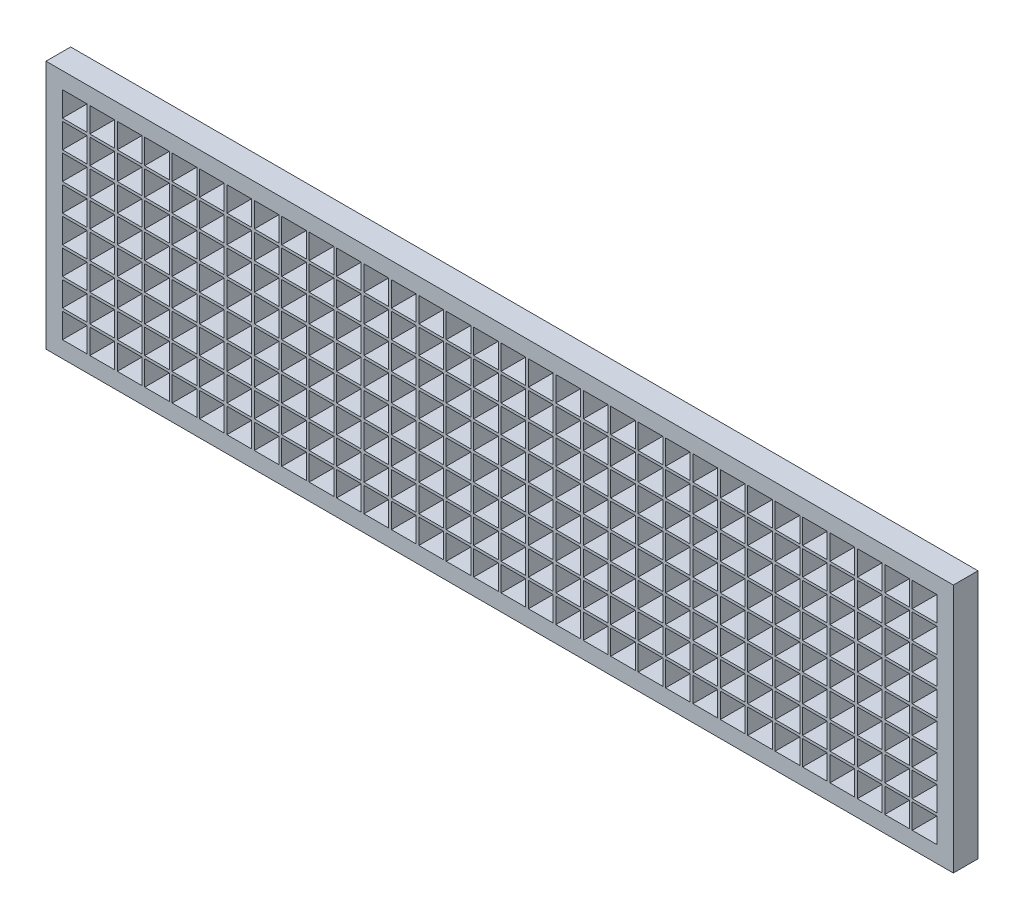
SolidWorks part; units mm, degrees
ref_plane "前视基准面" through (0, 0, 0) normal (0, 0, 1) x (1, 0, 0)
ref_plane "上视基准面" through (0, 0, 0) normal (0, 1, 0) x (1, 0, 0)
ref_plane "右视基准面" through (0, 0, 0) normal (1, 0, 0) x (0, 0, -1)
sketch "草图1" plane through (0, 0, 0) normal (0, 0, 1) x (1, 0, 0)
  line L0 (-21.8902, 5.9817) -> (-17.3902, 5.9817)
  line L1 (-26.8902, 5.9817) -> (-22.3902, 5.9817)
  line L2 (-26.8902, 5.9817) -> (-26.8902, 1.4817)
  line L3 (-26.8902, 1.4817) -> (-22.3902, 1.4817)
  line L4 (-22.3902, 5.9817) -> (-22.3902, 1.4817)
  line L5 (-21.8902, 5.9817) -> (-21.8902, 1.4817)
  line L6 (-21.8902, 1.4817) -> (-17.3902, 1.4817)
  line L7 (-17.3902, 5.9817) -> (-17.3902, 1.4817)
  line L8 (-16.8902, 5.9817) -> (-12.3902, 5.9817)
  line L9 (-16.8902, 5.9817) -> (-16.8902, 1.4817)
  line L10 (-16.8902, 1.4817) -> (-12.3902, 1.4817)
  line L11 (-12.3902, 5.9817) -> (-12.3902, 1.4817)
  line L12 (-11.8902, 5.9817) -> (-7.3902, 5.9817)
  line L13 (-11.8902, 5.9817) -> (-11.8902, 1.4817)
  line L14 (-11.8902, 1.4817) -> (-7.3902, 1.4817)
  line L15 (-7.3902, 5.9817) -> (-7.3902, 1.4817)
  line L16 (-6.8902, 5.9817) -> (-2.3902, 5.9817)
  line L17 (-6.8902, 5.9817) -> (-6.8902, 1.4817)
  line L18 (-6.8902, 1.4817) -> (-2.3902, 1.4817)
  line L19 (-2.3902, 5.9817) -> (-2.3902, 1.4817)
  line L20 (-1.8902, 5.9817) -> (2.6098, 5.9817)
  line L21 (-1.8902, 5.9817) -> (-1.8902, 1.4817)
  line L22 (-1.8902, 1.4817) -> (2.6098, 1.4817)
  line L23 (2.6098, 5.9817) -> (2.6098, 1.4817)
  line L24 (3.1098, 5.9817) -> (7.6098, 5.9817)
  line L25 (3.1098, 5.9817) -> (3.1098, 1.4817)
  line L26 (3.1098, 1.4817) -> (7.6098, 1.4817)
  line L27 (7.6098, 5.9817) -> (7.6098, 1.4817)
  line L28 (8.1098, 5.9817) -> (12.6098, 5.9817)
  line L29 (8.1098, 5.9817) -> (8.1098, 1.4817)
  line L30 (8.1098, 1.4817) -> (12.6098, 1.4817)
  line L31 (12.6098, 5.9817) -> (12.6098, 1.4817)
  line L32 (13.1098, 5.9817) -> (17.6098, 5.9817)
  line L33 (13.1098, 5.9817) -> (13.1098, 1.4817)
  line L34 (13.1098, 1.4817) -> (17.6098, 1.4817)
  line L35 (17.6098, 5.9817) -> (17.6098, 1.4817)
  line L36 (18.1098, 5.9817) -> (22.6098, 5.9817)
  line L37 (18.1098, 5.9817) -> (18.1098, 1.4817)
  line L38 (18.1098, 1.4817) -> (22.6098, 1.4817)
  line L39 (22.6098, 5.9817) -> (22.6098, 1.4817)
  line L40 (23.1098, 5.9817) -> (27.6098, 5.9817)
  line L41 (23.1098, 5.9817) -> (23.1098, 1.4817)
  line L42 (23.1098, 1.4817) -> (27.6098, 1.4817)
  line L43 (27.6098, 5.9817) -> (27.6098, 1.4817)
  line L44 (28.1098, 5.9817) -> (32.6098, 5.9817)
  line L45 (28.1098, 5.9817) -> (28.1098, 1.4817)
  line L46 (28.1098, 1.4817) -> (32.6098, 1.4817)
  line L47 (32.6098, 5.9817) -> (32.6098, 1.4817)
  line L48 (33.1098, 5.9817) -> (37.6098, 5.9817)
  line L49 (33.1098, 5.9817) -> (33.1098, 1.4817)
  line L50 (33.1098, 1.4817) -> (37.6098, 1.4817)
  line L51 (37.6098, 5.9817) -> (37.6098, 1.4817)
  line L52 (38.1098, 5.9817) -> (42.6098, 5.9817)
  line L53 (38.1098, 5.9817) -> (38.1098, 1.4817)
  line L54 (38.1098, 1.4817) -> (42.6098, 1.4817)
  line L55 (42.6098, 5.9817) -> (42.6098, 1.4817)
  line L56 (43.1098, 5.9817) -> (47.6098, 5.9817)
  line L57 (43.1098, 5.9817) -> (43.1098, 1.4817)
  line L58 (43.1098, 1.4817) -> (47.6098, 1.4817)
  line L59 (47.6098, 5.9817) -> (47.6098, 1.4817)
  line L60 (48.1098, 5.9817) -> (52.6098, 5.9817)
  line L61 (48.1098, 5.9817) -> (48.1098, 1.4817)
  line L62 (48.1098, 1.4817) -> (52.6098, 1.4817)
  line L63 (52.6098, 5.9817) -> (52.6098, 1.4817)
  line L64 (53.1098, 5.9817) -> (57.6098, 5.9817)
  line L65 (53.1098, 5.9817) -> (53.1098, 1.4817)
  line L66 (53.1098, 1.4817) -> (57.6098, 1.4817)
  line L67 (57.6098, 5.9817) -> (57.6098, 1.4817)
  line L68 (58.1098, 5.9817) -> (62.6098, 5.9817)
  line L69 (58.1098, 5.9817) -> (58.1098, 1.4817)
  line L70 (58.1098, 1.4817) -> (62.6098, 1.4817)
  line L71 (62.6098, 5.9817) -> (62.6098, 1.4817)
  line L72 (63.1098, 5.9817) -> (67.6098, 5.9817)
  line L73 (63.1098, 5.9817) -> (63.1098, 1.4817)
  line L74 (63.1098, 1.4817) -> (67.6098, 1.4817)
  line L75 (67.6098, 5.9817) -> (67.6098, 1.4817)
  line L76 (68.1098, 5.9817) -> (72.6098, 5.9817)
  line L77 (68.1098, 5.9817) -> (68.1098, 1.4817)
  line L78 (68.1098, 1.4817) -> (72.6098, 1.4817)
  line L79 (72.6098, 5.9817) -> (72.6098, 1.4817)
  line L80 (73.1098, 5.9817) -> (77.6098, 5.9817)
  line L81 (73.1098, 5.9817) -> (73.1098, 1.4817)
  line L82 (73.1098, 1.4817) -> (77.6098, 1.4817)
  line L83 (77.6098, 5.9817) -> (77.6098, 1.4817)
  line L84 (78.1098, 5.9817) -> (82.6098, 5.9817)
  line L85 (78.1098, 5.9817) -> (78.1098, 1.4817)
  line L86 (78.1098, 1.4817) -> (82.6098, 1.4817)
  line L87 (82.6098, 5.9817) -> (82.6098, 1.4817)
  line L88 (83.1098, 5.9817) -> (87.6098, 5.9817)
  line L89 (83.1098, 5.9817) -> (83.1098, 1.4817)
  line L90 (83.1098, 1.4817) -> (87.6098, 1.4817)
  line L91 (87.6098, 5.9817) -> (87.6098, 1.4817)
  line L92 (88.1098, 5.9817) -> (92.6098, 5.9817)
  line L93 (88.1098, 5.9817) -> (88.1098, 1.4817)
  line L94 (88.1098, 1.4817) -> (92.6098, 1.4817)
  line L95 (92.6098, 5.9817) -> (92.6098, 1.4817)
  line L96 (93.1098, 5.9817) -> (97.6098, 5.9817)
  line L97 (93.1098, 5.9817) -> (93.1098, 1.4817)
  line L98 (93.1098, 1.4817) -> (97.6098, 1.4817)
  line L99 (97.6098, 5.9817) -> (97.6098, 1.4817)
  line L100 (98.1098, 5.9817) -> (102.6098, 5.9817)
  line L101 (98.1098, 5.9817) -> (98.1098, 1.4817)
  line L102 (98.1098, 1.4817) -> (102.6098, 1.4817)
  line L103 (102.6098, 5.9817) -> (102.6098, 1.4817)
  line L104 (103.1098, 5.9817) -> (107.6098, 5.9817)
  line L105 (103.1098, 5.9817) -> (103.1098, 1.4817)
  line L106 (103.1098, 1.4817) -> (107.6098, 1.4817)
  line L107 (107.6098, 5.9817) -> (107.6098, 1.4817)
  line L108 (108.1098, 5.9817) -> (112.6098, 5.9817)
  line L109 (108.1098, 5.9817) -> (108.1098, 1.4817)
  line L110 (108.1098, 1.4817) -> (112.6098, 1.4817)
  line L111 (112.6098, 5.9817) -> (112.6098, 1.4817)
  line L112 (113.1098, 5.9817) -> (117.6098, 5.9817)
  line L113 (113.1098, 5.9817) -> (113.1098, 1.4817)
  line L114 (113.1098, 1.4817) -> (117.6098, 1.4817)
  line L115 (117.6098, 5.9817) -> (117.6098, 1.4817)
  line L116 (118.1098, 5.9817) -> (122.6098, 5.9817)
  line L117 (118.1098, 5.9817) -> (118.1098, 1.4817)
  line L118 (118.1098, 1.4817) -> (122.6098, 1.4817)
  line L119 (122.6098, 5.9817) -> (122.6098, 1.4817)
  line L120 (123.1098, 5.9817) -> (127.6098, 5.9817)
  line L121 (123.1098, 5.9817) -> (123.1098, 1.4817)
  line L122 (123.1098, 1.4817) -> (127.6098, 1.4817)
  line L123 (127.6098, 5.9817) -> (127.6098, 1.4817)
  line L124 (128.1098, 5.9817) -> (132.6098, 5.9817)
  line L125 (128.1098, 5.9817) -> (128.1098, 1.4817)
  line L126 (128.1098, 1.4817) -> (132.6098, 1.4817)
  line L127 (132.6098, 5.9817) -> (132.6098, 1.4817)
  line L128 (-21.8902, 10.9817) -> (-17.3902, 10.9817)
  line L129 (-21.8902, 10.9817) -> (-21.8902, 6.4817)
  line L130 (-21.8902, 6.4817) -> (-17.3902, 6.4817)
  line L131 (-17.3902, 10.9817) -> (-17.3902, 6.4817)
  line L132 (-16.8902, 10.9817) -> (-12.3902, 10.9817)
  line L133 (-16.8902, 10.9817) -> (-16.8902, 6.4817)
  line L134 (-16.8902, 6.4817) -> (-12.3902, 6.4817)
  line L135 (-12.3902, 10.9817) -> (-12.3902, 6.4817)
  line L136 (-11.8902, 10.9817) -> (-7.3902, 10.9817)
  line L137 (-11.8902, 10.9817) -> (-11.8902, 6.4817)
  line L138 (-11.8902, 6.4817) -> (-7.3902, 6.4817)
  line L139 (-7.3902, 10.9817) -> (-7.3902, 6.4817)
  line L140 (-6.8902, 10.9817) -> (-2.3902, 10.9817)
  line L141 (-6.8902, 10.9817) -> (-6.8902, 6.4817)
  line L142 (-6.8902, 6.4817) -> (-2.3902, 6.4817)
  line L143 (-2.3902, 10.9817) -> (-2.3902, 6.4817)
  line L144 (-1.8902, 10.9817) -> (2.6098, 10.9817)
  line L145 (-1.8902, 10.9817) -> (-1.8902, 6.4817)
  line L146 (-1.8902, 6.4817) -> (2.6098, 6.4817)
  line L147 (2.6098, 10.9817) -> (2.6098, 6.4817)
  line L148 (3.1098, 10.9817) -> (7.6098, 10.9817)
  line L149 (3.1098, 10.9817) -> (3.1098, 6.4817)
  line L150 (3.1098, 6.4817) -> (7.6098, 6.4817)
  line L151 (7.6098, 10.9817) -> (7.6098, 6.4817)
  line L152 (8.1098, 10.9817) -> (12.6098, 10.9817)
  line L153 (8.1098, 10.9817) -> (8.1098, 6.4817)
  line L154 (8.1098, 6.4817) -> (12.6098, 6.4817)
  line L155 (12.6098, 10.9817) -> (12.6098, 6.4817)
  line L156 (13.1098, 10.9817) -> (17.6098, 10.9817)
  line L157 (13.1098, 10.9817) -> (13.1098, 6.4817)
  line L158 (13.1098, 6.4817) -> (17.6098, 6.4817)
  line L159 (17.6098, 10.9817) -> (17.6098, 6.4817)
  line L160 (18.1098, 10.9817) -> (22.6098, 10.9817)
  line L161 (18.1098, 10.9817) -> (18.1098, 6.4817)
  line L162 (18.1098, 6.4817) -> (22.6098, 6.4817)
  line L163 (22.6098, 10.9817) -> (22.6098, 6.4817)
  line L164 (23.1098, 10.9817) -> (27.6098, 10.9817)
  line L165 (23.1098, 10.9817) -> (23.1098, 6.4817)
  line L166 (23.1098, 6.4817) -> (27.6098, 6.4817)
  line L167 (27.6098, 10.9817) -> (27.6098, 6.4817)
  line L168 (28.1098, 10.9817) -> (32.6098, 10.9817)
  line L169 (28.1098, 10.9817) -> (28.1098, 6.4817)
  line L170 (28.1098, 6.4817) -> (32.6098, 6.4817)
  line L171 (32.6098, 10.9817) -> (32.6098, 6.4817)
  line L172 (33.1098, 10.9817) -> (37.6098, 10.9817)
  line L173 (33.1098, 10.9817) -> (33.1098, 6.4817)
  line L174 (33.1098, 6.4817) -> (37.6098, 6.4817)
  line L175 (37.6098, 10.9817) -> (37.6098, 6.4817)
  line L176 (38.1098, 10.9817) -> (42.6098, 10.9817)
  line L177 (38.1098, 10.9817) -> (38.1098, 6.4817)
  line L178 (38.1098, 6.4817) -> (42.6098, 6.4817)
  line L179 (42.6098, 10.9817) -> (42.6098, 6.4817)
  line L180 (43.1098, 10.9817) -> (47.6098, 10.9817)
  line L181 (43.1098, 10.9817) -> (43.1098, 6.4817)
  line L182 (43.1098, 6.4817) -> (47.6098, 6.4817)
  line L183 (47.6098, 10.9817) -> (47.6098, 6.4817)
  line L184 (48.1098, 10.9817) -> (52.6098, 10.9817)
  line L185 (48.1098, 10.9817) -> (48.1098, 6.4817)
  line L186 (48.1098, 6.4817) -> (52.6098, 6.4817)
  line L187 (52.6098, 10.9817) -> (52.6098, 6.4817)
  line L188 (53.1098, 10.9817) -> (57.6098, 10.9817)
  line L189 (53.1098, 10.9817) -> (53.1098, 6.4817)
  line L190 (53.1098, 6.4817) -> (57.6098, 6.4817)
  line L191 (57.6098, 10.9817) -> (57.6098, 6.4817)
  line L192 (58.1098, 10.9817) -> (62.6098, 10.9817)
  line L193 (58.1098, 10.9817) -> (58.1098, 6.4817)
  line L194 (58.1098, 6.4817) -> (62.6098, 6.4817)
  line L195 (62.6098, 10.9817) -> (62.6098, 6.4817)
  line L196 (63.1098, 10.9817) -> (67.6098, 10.9817)
  line L197 (63.1098, 10.9817) -> (63.1098, 6.4817)
  line L198 (63.1098, 6.4817) -> (67.6098, 6.4817)
  line L199 (67.6098, 10.9817) -> (67.6098, 6.4817)
  line L200 (68.1098, 10.9817) -> (72.6098, 10.9817)
  line L201 (68.1098, 10.9817) -> (68.1098, 6.4817)
  line L202 (68.1098, 6.4817) -> (72.6098, 6.4817)
  line L203 (72.6098, 10.9817) -> (72.6098, 6.4817)
  line L204 (73.1098, 10.9817) -> (77.6098, 10.9817)
  line L205 (73.1098, 10.9817) -> (73.1098, 6.4817)
  line L206 (73.1098, 6.4817) -> (77.6098, 6.4817)
  line L207 (77.6098, 10.9817) -> (77.6098, 6.4817)
  line L208 (78.1098, 10.9817) -> (82.6098, 10.9817)
  line L209 (78.1098, 10.9817) -> (78.1098, 6.4817)
  line L210 (78.1098, 6.4817) -> (82.6098, 6.4817)
  line L211 (82.6098, 10.9817) -> (82.6098, 6.4817)
  line L212 (83.1098, 10.9817) -> (87.6098, 10.9817)
  line L213 (83.1098, 10.9817) -> (83.1098, 6.4817)
  line L214 (83.1098, 6.4817) -> (87.6098, 6.4817)
  line L215 (87.6098, 10.9817) -> (87.6098, 6.4817)
  line L216 (88.1098, 10.9817) -> (92.6098, 10.9817)
  line L217 (88.1098, 10.9817) -> (88.1098, 6.4817)
  line L218 (88.1098, 6.4817) -> (92.6098, 6.4817)
  line L219 (92.6098, 10.9817) -> (92.6098, 6.4817)
  line L220 (93.1098, 10.9817) -> (97.6098, 10.9817)
  line L221 (93.1098, 10.9817) -> (93.1098, 6.4817)
  line L222 (93.1098, 6.4817) -> (97.6098, 6.4817)
  line L223 (97.6098, 10.9817) -> (97.6098, 6.4817)
  line L224 (98.1098, 10.9817) -> (102.6098, 10.9817)
  line L225 (98.1098, 10.9817) -> (98.1098, 6.4817)
  line L226 (98.1098, 6.4817) -> (102.6098, 6.4817)
  line L227 (102.6098, 10.9817) -> (102.6098, 6.4817)
  line L228 (103.1098, 10.9817) -> (107.6098, 10.9817)
  line L229 (103.1098, 10.9817) -> (103.1098, 6.4817)
  line L230 (103.1098, 6.4817) -> (107.6098, 6.4817)
  line L231 (107.6098, 10.9817) -> (107.6098, 6.4817)
  line L232 (108.1098, 10.9817) -> (112.6098, 10.9817)
  line L233 (108.1098, 10.9817) -> (108.1098, 6.4817)
  line L234 (108.1098, 6.4817) -> (112.6098, 6.4817)
  line L235 (112.6098, 10.9817) -> (112.6098, 6.4817)
  line L236 (113.1098, 10.9817) -> (117.6098, 10.9817)
  line L237 (113.1098, 10.9817) -> (113.1098, 6.4817)
  line L238 (113.1098, 6.4817) -> (117.6098, 6.4817)
  line L239 (117.6098, 10.9817) -> (117.6098, 6.4817)
  line L240 (118.1098, 10.9817) -> (122.6098, 10.9817)
  line L241 (118.1098, 10.9817) -> (118.1098, 6.4817)
  line L242 (118.1098, 6.4817) -> (122.6098, 6.4817)
  line L243 (122.6098, 10.9817) -> (122.6098, 6.4817)
  line L244 (123.1098, 10.9817) -> (127.6098, 10.9817)
  line L245 (123.1098, 10.9817) -> (123.1098, 6.4817)
  line L246 (123.1098, 6.4817) -> (127.6098, 6.4817)
  line L247 (127.6098, 10.9817) -> (127.6098, 6.4817)
  line L248 (128.1098, 10.9817) -> (132.6098, 10.9817)
  line L249 (128.1098, 10.9817) -> (128.1098, 6.4817)
  line L250 (128.1098, 6.4817) -> (132.6098, 6.4817)
  line L251 (132.6098, 10.9817) -> (132.6098, 6.4817)
  line L252 (-21.8902, 15.9817) -> (-17.3902, 15.9817)
  line L253 (-21.8902, 15.9817) -> (-21.8902, 11.4817)
  line L254 (-21.8902, 11.4817) -> (-17.3902, 11.4817)
  line L255 (-17.3902, 15.9817) -> (-17.3902, 11.4817)
  line L256 (-16.8902, 15.9817) -> (-12.3902, 15.9817)
  line L257 (-16.8902, 15.9817) -> (-16.8902, 11.4817)
  line L258 (-16.8902, 11.4817) -> (-12.3902, 11.4817)
  line L259 (-12.3902, 15.9817) -> (-12.3902, 11.4817)
  line L260 (-11.8902, 15.9817) -> (-7.3902, 15.9817)
  line L261 (-11.8902, 15.9817) -> (-11.8902, 11.4817)
  line L262 (-11.8902, 11.4817) -> (-7.3902, 11.4817)
  line L263 (-7.3902, 15.9817) -> (-7.3902, 11.4817)
  line L264 (-6.8902, 15.9817) -> (-2.3902, 15.9817)
  line L265 (-6.8902, 15.9817) -> (-6.8902, 11.4817)
  line L266 (-6.8902, 11.4817) -> (-2.3902, 11.4817)
  line L267 (-2.3902, 15.9817) -> (-2.3902, 11.4817)
  line L268 (-1.8902, 15.9817) -> (2.6098, 15.9817)
  line L269 (-1.8902, 15.9817) -> (-1.8902, 11.4817)
  line L270 (-1.8902, 11.4817) -> (2.6098, 11.4817)
  line L271 (2.6098, 15.9817) -> (2.6098, 11.4817)
  line L272 (3.1098, 15.9817) -> (7.6098, 15.9817)
  line L273 (3.1098, 15.9817) -> (3.1098, 11.4817)
  line L274 (3.1098, 11.4817) -> (7.6098, 11.4817)
  line L275 (7.6098, 15.9817) -> (7.6098, 11.4817)
  line L276 (8.1098, 15.9817) -> (12.6098, 15.9817)
  line L277 (8.1098, 15.9817) -> (8.1098, 11.4817)
  line L278 (8.1098, 11.4817) -> (12.6098, 11.4817)
  line L279 (12.6098, 15.9817) -> (12.6098, 11.4817)
  line L280 (13.1098, 15.9817) -> (17.6098, 15.9817)
  line L281 (13.1098, 15.9817) -> (13.1098, 11.4817)
  line L282 (13.1098, 11.4817) -> (17.6098, 11.4817)
  line L283 (17.6098, 15.9817) -> (17.6098, 11.4817)
  line L284 (18.1098, 15.9817) -> (22.6098, 15.9817)
  line L285 (18.1098, 15.9817) -> (18.1098, 11.4817)
  line L286 (18.1098, 11.4817) -> (22.6098, 11.4817)
  line L287 (22.6098, 15.9817) -> (22.6098, 11.4817)
  line L288 (23.1098, 15.9817) -> (27.6098, 15.9817)
  line L289 (23.1098, 15.9817) -> (23.1098, 11.4817)
  line L290 (23.1098, 11.4817) -> (27.6098, 11.4817)
  line L291 (27.6098, 15.9817) -> (27.6098, 11.4817)
  line L292 (28.1098, 15.9817) -> (32.6098, 15.9817)
  line L293 (28.1098, 15.9817) -> (28.1098, 11.4817)
  line L294 (28.1098, 11.4817) -> (32.6098, 11.4817)
  line L295 (32.6098, 15.9817) -> (32.6098, 11.4817)
  line L296 (33.1098, 15.9817) -> (37.6098, 15.9817)
  line L297 (33.1098, 15.9817) -> (33.1098, 11.4817)
  line L298 (33.1098, 11.4817) -> (37.6098, 11.4817)
  line L299 (37.6098, 15.9817) -> (37.6098, 11.4817)
  line L300 (38.1098, 15.9817) -> (42.6098, 15.9817)
  line L301 (38.1098, 15.9817) -> (38.1098, 11.4817)
  line L302 (38.1098, 11.4817) -> (42.6098, 11.4817)
  line L303 (42.6098, 15.9817) -> (42.6098, 11.4817)
  line L304 (43.1098, 15.9817) -> (47.6098, 15.9817)
  line L305 (43.1098, 15.9817) -> (43.1098, 11.4817)
  line L306 (43.1098, 11.4817) -> (47.6098, 11.4817)
  line L307 (47.6098, 15.9817) -> (47.6098, 11.4817)
  line L308 (48.1098, 15.9817) -> (52.6098, 15.9817)
  line L309 (48.1098, 15.9817) -> (48.1098, 11.4817)
  line L310 (48.1098, 11.4817) -> (52.6098, 11.4817)
  line L311 (52.6098, 15.9817) -> (52.6098, 11.4817)
  line L312 (53.1098, 15.9817) -> (57.6098, 15.9817)
  line L313 (53.1098, 15.9817) -> (53.1098, 11.4817)
  line L314 (53.1098, 11.4817) -> (57.6098, 11.4817)
  line L315 (57.6098, 15.9817) -> (57.6098, 11.4817)
  line L316 (58.1098, 15.9817) -> (62.6098, 15.9817)
  line L317 (58.1098, 15.9817) -> (58.1098, 11.4817)
  line L318 (58.1098, 11.4817) -> (62.6098, 11.4817)
  line L319 (62.6098, 15.9817) -> (62.6098, 11.4817)
  line L320 (63.1098, 15.9817) -> (67.6098, 15.9817)
  line L321 (63.1098, 15.9817) -> (63.1098, 11.4817)
  line L322 (63.1098, 11.4817) -> (67.6098, 11.4817)
  line L323 (67.6098, 15.9817) -> (67.6098, 11.4817)
  line L324 (68.1098, 15.9817) -> (72.6098, 15.9817)
  line L325 (68.1098, 15.9817) -> (68.1098, 11.4817)
  line L326 (68.1098, 11.4817) -> (72.6098, 11.4817)
  line L327 (72.6098, 15.9817) -> (72.6098, 11.4817)
  line L328 (73.1098, 15.9817) -> (77.6098, 15.9817)
  line L329 (73.1098, 15.9817) -> (73.1098, 11.4817)
  line L330 (73.1098, 11.4817) -> (77.6098, 11.4817)
  line L331 (77.6098, 15.9817) -> (77.6098, 11.4817)
  line L332 (78.1098, 15.9817) -> (82.6098, 15.9817)
  line L333 (78.1098, 15.9817) -> (78.1098, 11.4817)
  line L334 (78.1098, 11.4817) -> (82.6098, 11.4817)
  line L335 (82.6098, 15.9817) -> (82.6098, 11.4817)
  line L336 (83.1098, 15.9817) -> (87.6098, 15.9817)
  line L337 (83.1098, 15.9817) -> (83.1098, 11.4817)
  line L338 (83.1098, 11.4817) -> (87.6098, 11.4817)
  line L339 (87.6098, 15.9817) -> (87.6098, 11.4817)
  line L340 (88.1098, 15.9817) -> (92.6098, 15.9817)
  line L341 (88.1098, 15.9817) -> (88.1098, 11.4817)
  line L342 (88.1098, 11.4817) -> (92.6098, 11.4817)
  line L343 (92.6098, 15.9817) -> (92.6098, 11.4817)
  line L344 (93.1098, 15.9817) -> (97.6098, 15.9817)
  line L345 (93.1098, 15.9817) -> (93.1098, 11.4817)
  line L346 (93.1098, 11.4817) -> (97.6098, 11.4817)
  line L347 (97.6098, 15.9817) -> (97.6098, 11.4817)
  line L348 (98.1098, 15.9817) -> (102.6098, 15.9817)
  line L349 (98.1098, 15.9817) -> (98.1098, 11.4817)
  line L350 (98.1098, 11.4817) -> (102.6098, 11.4817)
  line L351 (102.6098, 15.9817) -> (102.6098, 11.4817)
  line L352 (103.1098, 15.9817) -> (107.6098, 15.9817)
  line L353 (103.1098, 15.9817) -> (103.1098, 11.4817)
  line L354 (103.1098, 11.4817) -> (107.6098, 11.4817)
  line L355 (107.6098, 15.9817) -> (107.6098, 11.4817)
  line L356 (108.1098, 15.9817) -> (112.6098, 15.9817)
  line L357 (108.1098, 15.9817) -> (108.1098, 11.4817)
  line L358 (108.1098, 11.4817) -> (112.6098, 11.4817)
  line L359 (112.6098, 15.9817) -> (112.6098, 11.4817)
  line L360 (113.1098, 15.9817) -> (117.6098, 15.9817)
  line L361 (113.1098, 15.9817) -> (113.1098, 11.4817)
  line L362 (113.1098, 11.4817) -> (117.6098, 11.4817)
  line L363 (117.6098, 15.9817) -> (117.6098, 11.4817)
  line L364 (118.1098, 15.9817) -> (122.6098, 15.9817)
  line L365 (118.1098, 15.9817) -> (118.1098, 11.4817)
  line L366 (118.1098, 11.4817) -> (122.6098, 11.4817)
  line L367 (122.6098, 15.9817) -> (122.6098, 11.4817)
  line L368 (123.1098, 15.9817) -> (127.6098, 15.9817)
  line L369 (123.1098, 15.9817) -> (123.1098, 11.4817)
  line L370 (123.1098, 11.4817) -> (127.6098, 11.4817)
  line L371 (127.6098, 15.9817) -> (127.6098, 11.4817)
  line L372 (128.1098, 15.9817) -> (132.6098, 15.9817)
  line L373 (128.1098, 15.9817) -> (128.1098, 11.4817)
  line L374 (128.1098, 11.4817) -> (132.6098, 11.4817)
  line L375 (132.6098, 15.9817) -> (132.6098, 11.4817)
  line L376 (-21.8902, 20.9817) -> (-17.3902, 20.9817)
  line L377 (-21.8902, 20.9817) -> (-21.8902, 16.4817)
  line L378 (-21.8902, 16.4817) -> (-17.3902, 16.4817)
  line L379 (-17.3902, 20.9817) -> (-17.3902, 16.4817)
  line L380 (-16.8902, 20.9817) -> (-12.3902, 20.9817)
  line L381 (-16.8902, 20.9817) -> (-16.8902, 16.4817)
  line L382 (-16.8902, 16.4817) -> (-12.3902, 16.4817)
  line L383 (-12.3902, 20.9817) -> (-12.3902, 16.4817)
  line L384 (-11.8902, 20.9817) -> (-7.3902, 20.9817)
  line L385 (-11.8902, 20.9817) -> (-11.8902, 16.4817)
  line L386 (-11.8902, 16.4817) -> (-7.3902, 16.4817)
  line L387 (-7.3902, 20.9817) -> (-7.3902, 16.4817)
  line L388 (-6.8902, 20.9817) -> (-2.3902, 20.9817)
  line L389 (-6.8902, 20.9817) -> (-6.8902, 16.4817)
  line L390 (-6.8902, 16.4817) -> (-2.3902, 16.4817)
  line L391 (-2.3902, 20.9817) -> (-2.3902, 16.4817)
  line L392 (-1.8902, 20.9817) -> (2.6098, 20.9817)
  line L393 (-1.8902, 20.9817) -> (-1.8902, 16.4817)
  line L394 (-1.8902, 16.4817) -> (2.6098, 16.4817)
  line L395 (2.6098, 20.9817) -> (2.6098, 16.4817)
  line L396 (3.1098, 20.9817) -> (7.6098, 20.9817)
  line L397 (3.1098, 20.9817) -> (3.1098, 16.4817)
  line L398 (3.1098, 16.4817) -> (7.6098, 16.4817)
  line L399 (7.6098, 20.9817) -> (7.6098, 16.4817)
  line L400 (8.1098, 20.9817) -> (12.6098, 20.9817)
  line L401 (8.1098, 20.9817) -> (8.1098, 16.4817)
  line L402 (8.1098, 16.4817) -> (12.6098, 16.4817)
  line L403 (12.6098, 20.9817) -> (12.6098, 16.4817)
  line L404 (13.1098, 20.9817) -> (17.6098, 20.9817)
  line L405 (13.1098, 20.9817) -> (13.1098, 16.4817)
  line L406 (13.1098, 16.4817) -> (17.6098, 16.4817)
  line L407 (17.6098, 20.9817) -> (17.6098, 16.4817)
  line L408 (18.1098, 20.9817) -> (22.6098, 20.9817)
  line L409 (18.1098, 20.9817) -> (18.1098, 16.4817)
  line L410 (18.1098, 16.4817) -> (22.6098, 16.4817)
  line L411 (22.6098, 20.9817) -> (22.6098, 16.4817)
  line L412 (23.1098, 20.9817) -> (27.6098, 20.9817)
  line L413 (23.1098, 20.9817) -> (23.1098, 16.4817)
  line L414 (23.1098, 16.4817) -> (27.6098, 16.4817)
  line L415 (27.6098, 20.9817) -> (27.6098, 16.4817)
  line L416 (28.1098, 20.9817) -> (32.6098, 20.9817)
  line L417 (28.1098, 20.9817) -> (28.1098, 16.4817)
  line L418 (28.1098, 16.4817) -> (32.6098, 16.4817)
  line L419 (32.6098, 20.9817) -> (32.6098, 16.4817)
  line L420 (33.1098, 20.9817) -> (37.6098, 20.9817)
  line L421 (33.1098, 20.9817) -> (33.1098, 16.4817)
  line L422 (33.1098, 16.4817) -> (37.6098, 16.4817)
  line L423 (37.6098, 20.9817) -> (37.6098, 16.4817)
  line L424 (38.1098, 20.9817) -> (42.6098, 20.9817)
  line L425 (38.1098, 20.9817) -> (38.1098, 16.4817)
  line L426 (38.1098, 16.4817) -> (42.6098, 16.4817)
  line L427 (42.6098, 20.9817) -> (42.6098, 16.4817)
  line L428 (43.1098, 20.9817) -> (47.6098, 20.9817)
  line L429 (43.1098, 20.9817) -> (43.1098, 16.4817)
  line L430 (43.1098, 16.4817) -> (47.6098, 16.4817)
  line L431 (47.6098, 20.9817) -> (47.6098, 16.4817)
  line L432 (48.1098, 20.9817) -> (52.6098, 20.9817)
  line L433 (48.1098, 20.9817) -> (48.1098, 16.4817)
  line L434 (48.1098, 16.4817) -> (52.6098, 16.4817)
  line L435 (52.6098, 20.9817) -> (52.6098, 16.4817)
  line L436 (53.1098, 20.9817) -> (57.6098, 20.9817)
  line L437 (53.1098, 20.9817) -> (53.1098, 16.4817)
  line L438 (53.1098, 16.4817) -> (57.6098, 16.4817)
  line L439 (57.6098, 20.9817) -> (57.6098, 16.4817)
  line L440 (58.1098, 20.9817) -> (62.6098, 20.9817)
  line L441 (58.1098, 20.9817) -> (58.1098, 16.4817)
  line L442 (58.1098, 16.4817) -> (62.6098, 16.4817)
  line L443 (62.6098, 20.9817) -> (62.6098, 16.4817)
  line L444 (63.1098, 20.9817) -> (67.6098, 20.9817)
  line L445 (63.1098, 20.9817) -> (63.1098, 16.4817)
  line L446 (63.1098, 16.4817) -> (67.6098, 16.4817)
  line L447 (67.6098, 20.9817) -> (67.6098, 16.4817)
  line L448 (68.1098, 20.9817) -> (72.6098, 20.9817)
  line L449 (68.1098, 20.9817) -> (68.1098, 16.4817)
  line L450 (68.1098, 16.4817) -> (72.6098, 16.4817)
  line L451 (72.6098, 20.9817) -> (72.6098, 16.4817)
  line L452 (73.1098, 20.9817) -> (77.6098, 20.9817)
  line L453 (73.1098, 20.9817) -> (73.1098, 16.4817)
  line L454 (73.1098, 16.4817) -> (77.6098, 16.4817)
  line L455 (77.6098, 20.9817) -> (77.6098, 16.4817)
  line L456 (78.1098, 20.9817) -> (82.6098, 20.9817)
  line L457 (78.1098, 20.9817) -> (78.1098, 16.4817)
  line L458 (78.1098, 16.4817) -> (82.6098, 16.4817)
  line L459 (82.6098, 20.9817) -> (82.6098, 16.4817)
  line L460 (83.1098, 20.9817) -> (87.6098, 20.9817)
  line L461 (83.1098, 20.9817) -> (83.1098, 16.4817)
  line L462 (83.1098, 16.4817) -> (87.6098, 16.4817)
  line L463 (87.6098, 20.9817) -> (87.6098, 16.4817)
  line L464 (88.1098, 20.9817) -> (92.6098, 20.9817)
  line L465 (88.1098, 20.9817) -> (88.1098, 16.4817)
  line L466 (88.1098, 16.4817) -> (92.6098, 16.4817)
  line L467 (92.6098, 20.9817) -> (92.6098, 16.4817)
  line L468 (93.1098, 20.9817) -> (97.6098, 20.9817)
  line L469 (93.1098, 20.9817) -> (93.1098, 16.4817)
  line L470 (93.1098, 16.4817) -> (97.6098, 16.4817)
  line L471 (97.6098, 20.9817) -> (97.6098, 16.4817)
  line L472 (98.1098, 20.9817) -> (102.6098, 20.9817)
  line L473 (98.1098, 20.9817) -> (98.1098, 16.4817)
  line L474 (98.1098, 16.4817) -> (102.6098, 16.4817)
  line L475 (102.6098, 20.9817) -> (102.6098, 16.4817)
  line L476 (103.1098, 20.9817) -> (107.6098, 20.9817)
  line L477 (103.1098, 20.9817) -> (103.1098, 16.4817)
  line L478 (103.1098, 16.4817) -> (107.6098, 16.4817)
  line L479 (107.6098, 20.9817) -> (107.6098, 16.4817)
  line L480 (108.1098, 20.9817) -> (112.6098, 20.9817)
  line L481 (108.1098, 20.9817) -> (108.1098, 16.4817)
  line L482 (108.1098, 16.4817) -> (112.6098, 16.4817)
  line L483 (112.6098, 20.9817) -> (112.6098, 16.4817)
  line L484 (113.1098, 20.9817) -> (117.6098, 20.9817)
  line L485 (113.1098, 20.9817) -> (113.1098, 16.4817)
  line L486 (113.1098, 16.4817) -> (117.6098, 16.4817)
  line L487 (117.6098, 20.9817) -> (117.6098, 16.4817)
  line L488 (118.1098, 20.9817) -> (122.6098, 20.9817)
  line L489 (118.1098, 20.9817) -> (118.1098, 16.4817)
  line L490 (118.1098, 16.4817) -> (122.6098, 16.4817)
  line L491 (122.6098, 20.9817) -> (122.6098, 16.4817)
  line L492 (123.1098, 20.9817) -> (127.6098, 20.9817)
  line L493 (123.1098, 20.9817) -> (123.1098, 16.4817)
  line L494 (123.1098, 16.4817) -> (127.6098, 16.4817)
  line L495 (127.6098, 20.9817) -> (127.6098, 16.4817)
  line L496 (128.1098, 20.9817) -> (132.6098, 20.9817)
  line L497 (128.1098, 20.9817) -> (128.1098, 16.4817)
  line L498 (128.1098, 16.4817) -> (132.6098, 16.4817)
  line L499 (132.6098, 20.9817) -> (132.6098, 16.4817)
  line L500 (-21.8902, 25.9817) -> (-17.3902, 25.9817)
  line L501 (-21.8902, 25.9817) -> (-21.8902, 21.4817)
  line L502 (-21.8902, 21.4817) -> (-17.3902, 21.4817)
  line L503 (-17.3902, 25.9817) -> (-17.3902, 21.4817)
  line L504 (-16.8902, 25.9817) -> (-12.3902, 25.9817)
  line L505 (-16.8902, 25.9817) -> (-16.8902, 21.4817)
  line L506 (-16.8902, 21.4817) -> (-12.3902, 21.4817)
  line L507 (-12.3902, 25.9817) -> (-12.3902, 21.4817)
  line L508 (-11.8902, 25.9817) -> (-7.3902, 25.9817)
  line L509 (-11.8902, 25.9817) -> (-11.8902, 21.4817)
  line L510 (-11.8902, 21.4817) -> (-7.3902, 21.4817)
  line L511 (-7.3902, 25.9817) -> (-7.3902, 21.4817)
  line L512 (-6.8902, 25.9817) -> (-2.3902, 25.9817)
  line L513 (-6.8902, 25.9817) -> (-6.8902, 21.4817)
  line L514 (-6.8902, 21.4817) -> (-2.3902, 21.4817)
  line L515 (-2.3902, 25.9817) -> (-2.3902, 21.4817)
  line L516 (-1.8902, 25.9817) -> (2.6098, 25.9817)
  line L517 (-1.8902, 25.9817) -> (-1.8902, 21.4817)
  line L518 (-1.8902, 21.4817) -> (2.6098, 21.4817)
  line L519 (2.6098, 25.9817) -> (2.6098, 21.4817)
  line L520 (3.1098, 25.9817) -> (7.6098, 25.9817)
  line L521 (3.1098, 25.9817) -> (3.1098, 21.4817)
  line L522 (3.1098, 21.4817) -> (7.6098, 21.4817)
  line L523 (7.6098, 25.9817) -> (7.6098, 21.4817)
  line L524 (8.1098, 25.9817) -> (12.6098, 25.9817)
  line L525 (8.1098, 25.9817) -> (8.1098, 21.4817)
  line L526 (8.1098, 21.4817) -> (12.6098, 21.4817)
  line L527 (12.6098, 25.9817) -> (12.6098, 21.4817)
  line L528 (13.1098, 25.9817) -> (17.6098, 25.9817)
  line L529 (13.1098, 25.9817) -> (13.1098, 21.4817)
  line L530 (13.1098, 21.4817) -> (17.6098, 21.4817)
  line L531 (17.6098, 25.9817) -> (17.6098, 21.4817)
  line L532 (18.1098, 25.9817) -> (22.6098, 25.9817)
  line L533 (18.1098, 25.9817) -> (18.1098, 21.4817)
  line L534 (18.1098, 21.4817) -> (22.6098, 21.4817)
  line L535 (22.6098, 25.9817) -> (22.6098, 21.4817)
  line L536 (23.1098, 25.9817) -> (27.6098, 25.9817)
  line L537 (23.1098, 25.9817) -> (23.1098, 21.4817)
  line L538 (23.1098, 21.4817) -> (27.6098, 21.4817)
  line L539 (27.6098, 25.9817) -> (27.6098, 21.4817)
  line L540 (28.1098, 25.9817) -> (32.6098, 25.9817)
  line L541 (28.1098, 25.9817) -> (28.1098, 21.4817)
  line L542 (28.1098, 21.4817) -> (32.6098, 21.4817)
  line L543 (32.6098, 25.9817) -> (32.6098, 21.4817)
  line L544 (33.1098, 25.9817) -> (37.6098, 25.9817)
  line L545 (33.1098, 25.9817) -> (33.1098, 21.4817)
  line L546 (33.1098, 21.4817) -> (37.6098, 21.4817)
  line L547 (37.6098, 25.9817) -> (37.6098, 21.4817)
  line L548 (38.1098, 25.9817) -> (42.6098, 25.9817)
  line L549 (38.1098, 25.9817) -> (38.1098, 21.4817)
  line L550 (38.1098, 21.4817) -> (42.6098, 21.4817)
  line L551 (42.6098, 25.9817) -> (42.6098, 21.4817)
  line L552 (43.1098, 25.9817) -> (47.6098, 25.9817)
  line L553 (43.1098, 25.9817) -> (43.1098, 21.4817)
  line L554 (43.1098, 21.4817) -> (47.6098, 21.4817)
  line L555 (47.6098, 25.9817) -> (47.6098, 21.4817)
  line L556 (48.1098, 25.9817) -> (52.6098, 25.9817)
  line L557 (48.1098, 25.9817) -> (48.1098, 21.4817)
  line L558 (48.1098, 21.4817) -> (52.6098, 21.4817)
  line L559 (52.6098, 25.9817) -> (52.6098, 21.4817)
  line L560 (53.1098, 25.9817) -> (57.6098, 25.9817)
  line L561 (53.1098, 25.9817) -> (53.1098, 21.4817)
  line L562 (53.1098, 21.4817) -> (57.6098, 21.4817)
  line L563 (57.6098, 25.9817) -> (57.6098, 21.4817)
  line L564 (58.1098, 25.9817) -> (62.6098, 25.9817)
  line L565 (58.1098, 25.9817) -> (58.1098, 21.4817)
  line L566 (58.1098, 21.4817) -> (62.6098, 21.4817)
  line L567 (62.6098, 25.9817) -> (62.6098, 21.4817)
  line L568 (63.1098, 25.9817) -> (67.6098, 25.9817)
  line L569 (63.1098, 25.9817) -> (63.1098, 21.4817)
  line L570 (63.1098, 21.4817) -> (67.6098, 21.4817)
  line L571 (67.6098, 25.9817) -> (67.6098, 21.4817)
  line L572 (68.1098, 25.9817) -> (72.6098, 25.9817)
  line L573 (68.1098, 25.9817) -> (68.1098, 21.4817)
  line L574 (68.1098, 21.4817) -> (72.6098, 21.4817)
  line L575 (72.6098, 25.9817) -> (72.6098, 21.4817)
  line L576 (73.1098, 25.9817) -> (77.6098, 25.9817)
  line L577 (73.1098, 25.9817) -> (73.1098, 21.4817)
  line L578 (73.1098, 21.4817) -> (77.6098, 21.4817)
  line L579 (77.6098, 25.9817) -> (77.6098, 21.4817)
  line L580 (78.1098, 25.9817) -> (82.6098, 25.9817)
  line L581 (78.1098, 25.9817) -> (78.1098, 21.4817)
  line L582 (78.1098, 21.4817) -> (82.6098, 21.4817)
  line L583 (82.6098, 25.9817) -> (82.6098, 21.4817)
  line L584 (83.1098, 25.9817) -> (87.6098, 25.9817)
  line L585 (83.1098, 25.9817) -> (83.1098, 21.4817)
  line L586 (83.1098, 21.4817) -> (87.6098, 21.4817)
  line L587 (87.6098, 25.9817) -> (87.6098, 21.4817)
  line L588 (88.1098, 25.9817) -> (92.6098, 25.9817)
  line L589 (88.1098, 25.9817) -> (88.1098, 21.4817)
  line L590 (88.1098, 21.4817) -> (92.6098, 21.4817)
  line L591 (92.6098, 25.9817) -> (92.6098, 21.4817)
  line L592 (93.1098, 25.9817) -> (97.6098, 25.9817)
  line L593 (93.1098, 25.9817) -> (93.1098, 21.4817)
  line L594 (93.1098, 21.4817) -> (97.6098, 21.4817)
  line L595 (97.6098, 25.9817) -> (97.6098, 21.4817)
  line L596 (98.1098, 25.9817) -> (102.6098, 25.9817)
  line L597 (98.1098, 25.9817) -> (98.1098, 21.4817)
  line L598 (98.1098, 21.4817) -> (102.6098, 21.4817)
  line L599 (102.6098, 25.9817) -> (102.6098, 21.4817)
  line L600 (103.1098, 25.9817) -> (107.6098, 25.9817)
  line L601 (103.1098, 25.9817) -> (103.1098, 21.4817)
  line L602 (103.1098, 21.4817) -> (107.6098, 21.4817)
  line L603 (107.6098, 25.9817) -> (107.6098, 21.4817)
  line L604 (108.1098, 25.9817) -> (112.6098, 25.9817)
  line L605 (108.1098, 25.9817) -> (108.1098, 21.4817)
  line L606 (108.1098, 21.4817) -> (112.6098, 21.4817)
  line L607 (112.6098, 25.9817) -> (112.6098, 21.4817)
  line L608 (113.1098, 25.9817) -> (117.6098, 25.9817)
  line L609 (113.1098, 25.9817) -> (113.1098, 21.4817)
  line L610 (113.1098, 21.4817) -> (117.6098, 21.4817)
  line L611 (117.6098, 25.9817) -> (117.6098, 21.4817)
  line L612 (118.1098, 25.9817) -> (122.6098, 25.9817)
  line L613 (118.1098, 25.9817) -> (118.1098, 21.4817)
  line L614 (118.1098, 21.4817) -> (122.6098, 21.4817)
  line L615 (122.6098, 25.9817) -> (122.6098, 21.4817)
  line L616 (123.1098, 25.9817) -> (127.6098, 25.9817)
  line L617 (123.1098, 25.9817) -> (123.1098, 21.4817)
  line L618 (123.1098, 21.4817) -> (127.6098, 21.4817)
  line L619 (127.6098, 25.9817) -> (127.6098, 21.4817)
  line L620 (128.1098, 25.9817) -> (132.6098, 25.9817)
  line L621 (128.1098, 25.9817) -> (128.1098, 21.4817)
  line L622 (128.1098, 21.4817) -> (132.6098, 21.4817)
  line L623 (132.6098, 25.9817) -> (132.6098, 21.4817)
  line L624 (-21.8902, 30.9817) -> (-17.3902, 30.9817)
  line L625 (-21.8902, 30.9817) -> (-21.8902, 26.4817)
  line L626 (-21.8902, 26.4817) -> (-17.3902, 26.4817)
  line L627 (-17.3902, 30.9817) -> (-17.3902, 26.4817)
  line L628 (-16.8902, 30.9817) -> (-12.3902, 30.9817)
  line L629 (-16.8902, 30.9817) -> (-16.8902, 26.4817)
  line L630 (-16.8902, 26.4817) -> (-12.3902, 26.4817)
  line L631 (-12.3902, 30.9817) -> (-12.3902, 26.4817)
  line L632 (-11.8902, 30.9817) -> (-7.3902, 30.9817)
  line L633 (-11.8902, 30.9817) -> (-11.8902, 26.4817)
  line L634 (-11.8902, 26.4817) -> (-7.3902, 26.4817)
  line L635 (-7.3902, 30.9817) -> (-7.3902, 26.4817)
  line L636 (-6.8902, 30.9817) -> (-2.3902, 30.9817)
  line L637 (-6.8902, 30.9817) -> (-6.8902, 26.4817)
  line L638 (-6.8902, 26.4817) -> (-2.3902, 26.4817)
  line L639 (-2.3902, 30.9817) -> (-2.3902, 26.4817)
  line L640 (-1.8902, 30.9817) -> (2.6098, 30.9817)
  line L641 (-1.8902, 30.9817) -> (-1.8902, 26.4817)
  line L642 (-1.8902, 26.4817) -> (2.6098, 26.4817)
  line L643 (2.6098, 30.9817) -> (2.6098, 26.4817)
  line L644 (3.1098, 30.9817) -> (7.6098, 30.9817)
  line L645 (3.1098, 30.9817) -> (3.1098, 26.4817)
  line L646 (3.1098, 26.4817) -> (7.6098, 26.4817)
  line L647 (7.6098, 30.9817) -> (7.6098, 26.4817)
  line L648 (8.1098, 30.9817) -> (12.6098, 30.9817)
  line L649 (8.1098, 30.9817) -> (8.1098, 26.4817)
  line L650 (8.1098, 26.4817) -> (12.6098, 26.4817)
  line L651 (12.6098, 30.9817) -> (12.6098, 26.4817)
  line L652 (13.1098, 30.9817) -> (17.6098, 30.9817)
  line L653 (13.1098, 30.9817) -> (13.1098, 26.4817)
  line L654 (13.1098, 26.4817) -> (17.6098, 26.4817)
  line L655 (17.6098, 30.9817) -> (17.6098, 26.4817)
  line L656 (18.1098, 30.9817) -> (22.6098, 30.9817)
  line L657 (18.1098, 30.9817) -> (18.1098, 26.4817)
  line L658 (18.1098, 26.4817) -> (22.6098, 26.4817)
  line L659 (22.6098, 30.9817) -> (22.6098, 26.4817)
  line L660 (23.1098, 30.9817) -> (27.6098, 30.9817)
  line L661 (23.1098, 30.9817) -> (23.1098, 26.4817)
  line L662 (23.1098, 26.4817) -> (27.6098, 26.4817)
  line L663 (27.6098, 30.9817) -> (27.6098, 26.4817)
  line L664 (28.1098, 30.9817) -> (32.6098, 30.9817)
  line L665 (28.1098, 30.9817) -> (28.1098, 26.4817)
  line L666 (28.1098, 26.4817) -> (32.6098, 26.4817)
  line L667 (32.6098, 30.9817) -> (32.6098, 26.4817)
  line L668 (33.1098, 30.9817) -> (37.6098, 30.9817)
  line L669 (33.1098, 30.9817) -> (33.1098, 26.4817)
  line L670 (33.1098, 26.4817) -> (37.6098, 26.4817)
  line L671 (37.6098, 30.9817) -> (37.6098, 26.4817)
  line L672 (38.1098, 30.9817) -> (42.6098, 30.9817)
  line L673 (38.1098, 30.9817) -> (38.1098, 26.4817)
  line L674 (38.1098, 26.4817) -> (42.6098, 26.4817)
  line L675 (42.6098, 30.9817) -> (42.6098, 26.4817)
  line L676 (43.1098, 30.9817) -> (47.6098, 30.9817)
  line L677 (43.1098, 30.9817) -> (43.1098, 26.4817)
  line L678 (43.1098, 26.4817) -> (47.6098, 26.4817)
  line L679 (47.6098, 30.9817) -> (47.6098, 26.4817)
  line L680 (48.1098, 30.9817) -> (52.6098, 30.9817)
  line L681 (48.1098, 30.9817) -> (48.1098, 26.4817)
  line L682 (48.1098, 26.4817) -> (52.6098, 26.4817)
  line L683 (52.6098, 30.9817) -> (52.6098, 26.4817)
  line L684 (53.1098, 30.9817) -> (57.6098, 30.9817)
  line L685 (53.1098, 30.9817) -> (53.1098, 26.4817)
  line L686 (53.1098, 26.4817) -> (57.6098, 26.4817)
  line L687 (57.6098, 30.9817) -> (57.6098, 26.4817)
  line L688 (58.1098, 30.9817) -> (62.6098, 30.9817)
  line L689 (58.1098, 30.9817) -> (58.1098, 26.4817)
  line L690 (58.1098, 26.4817) -> (62.6098, 26.4817)
  line L691 (62.6098, 30.9817) -> (62.6098, 26.4817)
  line L692 (63.1098, 30.9817) -> (67.6098, 30.9817)
  line L693 (63.1098, 30.9817) -> (63.1098, 26.4817)
  line L694 (63.1098, 26.4817) -> (67.6098, 26.4817)
  line L695 (67.6098, 30.9817) -> (67.6098, 26.4817)
  line L696 (68.1098, 30.9817) -> (72.6098, 30.9817)
  line L697 (68.1098, 30.9817) -> (68.1098, 26.4817)
  line L698 (68.1098, 26.4817) -> (72.6098, 26.4817)
  line L699 (72.6098, 30.9817) -> (72.6098, 26.4817)
  line L700 (73.1098, 30.9817) -> (77.6098, 30.9817)
  line L701 (73.1098, 30.9817) -> (73.1098, 26.4817)
  line L702 (73.1098, 26.4817) -> (77.6098, 26.4817)
  line L703 (77.6098, 30.9817) -> (77.6098, 26.4817)
  line L704 (78.1098, 30.9817) -> (82.6098, 30.9817)
  line L705 (78.1098, 30.9817) -> (78.1098, 26.4817)
  line L706 (78.1098, 26.4817) -> (82.6098, 26.4817)
  line L707 (82.6098, 30.9817) -> (82.6098, 26.4817)
  line L708 (83.1098, 30.9817) -> (87.6098, 30.9817)
  line L709 (83.1098, 30.9817) -> (83.1098, 26.4817)
  line L710 (83.1098, 26.4817) -> (87.6098, 26.4817)
  line L711 (87.6098, 30.9817) -> (87.6098, 26.4817)
  line L712 (88.1098, 30.9817) -> (92.6098, 30.9817)
  line L713 (88.1098, 30.9817) -> (88.1098, 26.4817)
  line L714 (88.1098, 26.4817) -> (92.6098, 26.4817)
  line L715 (92.6098, 30.9817) -> (92.6098, 26.4817)
  line L716 (93.1098, 30.9817) -> (97.6098, 30.9817)
  line L717 (93.1098, 30.9817) -> (93.1098, 26.4817)
  line L718 (93.1098, 26.4817) -> (97.6098, 26.4817)
  line L719 (97.6098, 30.9817) -> (97.6098, 26.4817)
  line L720 (98.1098, 30.9817) -> (102.6098, 30.9817)
  line L721 (98.1098, 30.9817) -> (98.1098, 26.4817)
  line L722 (98.1098, 26.4817) -> (102.6098, 26.4817)
  line L723 (102.6098, 30.9817) -> (102.6098, 26.4817)
  line L724 (103.1098, 30.9817) -> (107.6098, 30.9817)
  line L725 (103.1098, 30.9817) -> (103.1098, 26.4817)
  line L726 (103.1098, 26.4817) -> (107.6098, 26.4817)
  line L727 (107.6098, 30.9817) -> (107.6098, 26.4817)
  line L728 (108.1098, 30.9817) -> (112.6098, 30.9817)
  line L729 (108.1098, 30.9817) -> (108.1098, 26.4817)
  line L730 (108.1098, 26.4817) -> (112.6098, 26.4817)
  line L731 (112.6098, 30.9817) -> (112.6098, 26.4817)
  line L732 (113.1098, 30.9817) -> (117.6098, 30.9817)
  line L733 (113.1098, 30.9817) -> (113.1098, 26.4817)
  line L734 (113.1098, 26.4817) -> (117.6098, 26.4817)
  line L735 (117.6098, 30.9817) -> (117.6098, 26.4817)
  line L736 (118.1098, 30.9817) -> (122.6098, 30.9817)
  line L737 (118.1098, 30.9817) -> (118.1098, 26.4817)
  line L738 (118.1098, 26.4817) -> (122.6098, 26.4817)
  line L739 (122.6098, 30.9817) -> (122.6098, 26.4817)
  line L740 (123.1098, 30.9817) -> (127.6098, 30.9817)
  line L741 (123.1098, 30.9817) -> (123.1098, 26.4817)
  line L742 (123.1098, 26.4817) -> (127.6098, 26.4817)
  line L743 (127.6098, 30.9817) -> (127.6098, 26.4817)
  line L744 (128.1098, 30.9817) -> (132.6098, 30.9817)
  line L745 (128.1098, 30.9817) -> (128.1098, 26.4817)
  line L746 (128.1098, 26.4817) -> (132.6098, 26.4817)
  line L747 (132.6098, 30.9817) -> (132.6098, 26.4817)
  line L748 (-21.8902, 35.9817) -> (-17.3902, 35.9817)
  line L749 (-21.8902, 35.9817) -> (-21.8902, 31.4817)
  line L750 (-21.8902, 31.4817) -> (-17.3902, 31.4817)
  line L751 (-17.3902, 35.9817) -> (-17.3902, 31.4817)
  line L752 (-16.8902, 35.9817) -> (-12.3902, 35.9817)
  line L753 (-16.8902, 35.9817) -> (-16.8902, 31.4817)
  line L754 (-16.8902, 31.4817) -> (-12.3902, 31.4817)
  line L755 (-12.3902, 35.9817) -> (-12.3902, 31.4817)
  line L756 (-11.8902, 35.9817) -> (-7.3902, 35.9817)
  line L757 (-11.8902, 35.9817) -> (-11.8902, 31.4817)
  line L758 (-11.8902, 31.4817) -> (-7.3902, 31.4817)
  line L759 (-7.3902, 35.9817) -> (-7.3902, 31.4817)
  line L760 (-6.8902, 35.9817) -> (-2.3902, 35.9817)
  line L761 (-6.8902, 35.9817) -> (-6.8902, 31.4817)
  line L762 (-6.8902, 31.4817) -> (-2.3902, 31.4817)
  line L763 (-2.3902, 35.9817) -> (-2.3902, 31.4817)
  line L764 (-1.8902, 35.9817) -> (2.6098, 35.9817)
  line L765 (-1.8902, 35.9817) -> (-1.8902, 31.4817)
  line L766 (-1.8902, 31.4817) -> (2.6098, 31.4817)
  line L767 (2.6098, 35.9817) -> (2.6098, 31.4817)
  line L768 (3.1098, 35.9817) -> (7.6098, 35.9817)
  line L769 (3.1098, 35.9817) -> (3.1098, 31.4817)
  line L770 (3.1098, 31.4817) -> (7.6098, 31.4817)
  line L771 (7.6098, 35.9817) -> (7.6098, 31.4817)
  line L772 (8.1098, 35.9817) -> (12.6098, 35.9817)
  line L773 (8.1098, 35.9817) -> (8.1098, 31.4817)
  line L774 (8.1098, 31.4817) -> (12.6098, 31.4817)
  line L775 (12.6098, 35.9817) -> (12.6098, 31.4817)
  line L776 (13.1098, 35.9817) -> (17.6098, 35.9817)
  line L777 (13.1098, 35.9817) -> (13.1098, 31.4817)
  line L778 (13.1098, 31.4817) -> (17.6098, 31.4817)
  line L779 (17.6098, 35.9817) -> (17.6098, 31.4817)
  line L780 (18.1098, 35.9817) -> (22.6098, 35.9817)
  line L781 (18.1098, 35.9817) -> (18.1098, 31.4817)
  line L782 (18.1098, 31.4817) -> (22.6098, 31.4817)
  line L783 (22.6098, 35.9817) -> (22.6098, 31.4817)
  line L784 (23.1098, 35.9817) -> (27.6098, 35.9817)
  line L785 (23.1098, 35.9817) -> (23.1098, 31.4817)
  line L786 (23.1098, 31.4817) -> (27.6098, 31.4817)
  line L787 (27.6098, 35.9817) -> (27.6098, 31.4817)
  line L788 (28.1098, 35.9817) -> (32.6098, 35.9817)
  line L789 (28.1098, 35.9817) -> (28.1098, 31.4817)
  line L790 (28.1098, 31.4817) -> (32.6098, 31.4817)
  line L791 (32.6098, 35.9817) -> (32.6098, 31.4817)
  line L792 (33.1098, 35.9817) -> (37.6098, 35.9817)
  line L793 (33.1098, 35.9817) -> (33.1098, 31.4817)
  line L794 (33.1098, 31.4817) -> (37.6098, 31.4817)
  line L795 (37.6098, 35.9817) -> (37.6098, 31.4817)
  line L796 (38.1098, 35.9817) -> (42.6098, 35.9817)
  line L797 (38.1098, 35.9817) -> (38.1098, 31.4817)
  line L798 (38.1098, 31.4817) -> (42.6098, 31.4817)
  line L799 (42.6098, 35.9817) -> (42.6098, 31.4817)
  line L800 (43.1098, 35.9817) -> (47.6098, 35.9817)
  line L801 (43.1098, 35.9817) -> (43.1098, 31.4817)
  line L802 (43.1098, 31.4817) -> (47.6098, 31.4817)
  line L803 (47.6098, 35.9817) -> (47.6098, 31.4817)
  line L804 (48.1098, 35.9817) -> (52.6098, 35.9817)
  line L805 (48.1098, 35.9817) -> (48.1098, 31.4817)
  line L806 (48.1098, 31.4817) -> (52.6098, 31.4817)
  line L807 (52.6098, 35.9817) -> (52.6098, 31.4817)
  line L808 (53.1098, 35.9817) -> (57.6098, 35.9817)
  line L809 (53.1098, 35.9817) -> (53.1098, 31.4817)
  line L810 (53.1098, 31.4817) -> (57.6098, 31.4817)
  line L811 (57.6098, 35.9817) -> (57.6098, 31.4817)
  line L812 (58.1098, 35.9817) -> (62.6098, 35.9817)
  line L813 (58.1098, 35.9817) -> (58.1098, 31.4817)
  line L814 (58.1098, 31.4817) -> (62.6098, 31.4817)
  line L815 (62.6098, 35.9817) -> (62.6098, 31.4817)
  line L816 (63.1098, 35.9817) -> (67.6098, 35.9817)
  line L817 (63.1098, 35.9817) -> (63.1098, 31.4817)
  line L818 (63.1098, 31.4817) -> (67.6098, 31.4817)
  line L819 (67.6098, 35.9817) -> (67.6098, 31.4817)
  line L820 (68.1098, 35.9817) -> (72.6098, 35.9817)
  line L821 (68.1098, 35.9817) -> (68.1098, 31.4817)
  line L822 (68.1098, 31.4817) -> (72.6098, 31.4817)
  line L823 (72.6098, 35.9817) -> (72.6098, 31.4817)
  line L824 (73.1098, 35.9817) -> (77.6098, 35.9817)
  line L825 (73.1098, 35.9817) -> (73.1098, 31.4817)
  line L826 (73.1098, 31.4817) -> (77.6098, 31.4817)
  line L827 (77.6098, 35.9817) -> (77.6098, 31.4817)
  line L828 (78.1098, 35.9817) -> (82.6098, 35.9817)
  line L829 (78.1098, 35.9817) -> (78.1098, 31.4817)
  line L830 (78.1098, 31.4817) -> (82.6098, 31.4817)
  line L831 (82.6098, 35.9817) -> (82.6098, 31.4817)
  line L832 (83.1098, 35.9817) -> (87.6098, 35.9817)
  line L833 (83.1098, 35.9817) -> (83.1098, 31.4817)
  line L834 (83.1098, 31.4817) -> (87.6098, 31.4817)
  line L835 (87.6098, 35.9817) -> (87.6098, 31.4817)
  line L836 (88.1098, 35.9817) -> (92.6098, 35.9817)
  line L837 (88.1098, 35.9817) -> (88.1098, 31.4817)
  line L838 (88.1098, 31.4817) -> (92.6098, 31.4817)
  line L839 (92.6098, 35.9817) -> (92.6098, 31.4817)
  line L840 (93.1098, 35.9817) -> (97.6098, 35.9817)
  line L841 (93.1098, 35.9817) -> (93.1098, 31.4817)
  line L842 (93.1098, 31.4817) -> (97.6098, 31.4817)
  line L843 (97.6098, 35.9817) -> (97.6098, 31.4817)
  line L844 (98.1098, 35.9817) -> (102.6098, 35.9817)
  line L845 (98.1098, 35.9817) -> (98.1098, 31.4817)
  line L846 (98.1098, 31.4817) -> (102.6098, 31.4817)
  line L847 (102.6098, 35.9817) -> (102.6098, 31.4817)
  line L848 (103.1098, 35.9817) -> (107.6098, 35.9817)
  line L849 (103.1098, 35.9817) -> (103.1098, 31.4817)
  line L850 (103.1098, 31.4817) -> (107.6098, 31.4817)
  line L851 (107.6098, 35.9817) -> (107.6098, 31.4817)
  line L852 (108.1098, 35.9817) -> (112.6098, 35.9817)
  line L853 (108.1098, 35.9817) -> (108.1098, 31.4817)
  line L854 (108.1098, 31.4817) -> (112.6098, 31.4817)
  line L855 (112.6098, 35.9817) -> (112.6098, 31.4817)
  line L856 (113.1098, 35.9817) -> (117.6098, 35.9817)
  line L857 (113.1098, 35.9817) -> (113.1098, 31.4817)
  line L858 (113.1098, 31.4817) -> (117.6098, 31.4817)
  line L859 (117.6098, 35.9817) -> (117.6098, 31.4817)
  line L860 (118.1098, 35.9817) -> (122.6098, 35.9817)
  line L861 (118.1098, 35.9817) -> (118.1098, 31.4817)
  line L862 (118.1098, 31.4817) -> (122.6098, 31.4817)
  line L863 (122.6098, 35.9817) -> (122.6098, 31.4817)
  line L864 (123.1098, 35.9817) -> (127.6098, 35.9817)
  line L865 (123.1098, 35.9817) -> (123.1098, 31.4817)
  line L866 (123.1098, 31.4817) -> (127.6098, 31.4817)
  line L867 (127.6098, 35.9817) -> (127.6098, 31.4817)
  line L868 (128.1098, 35.9817) -> (132.6098, 35.9817)
  line L869 (128.1098, 35.9817) -> (128.1098, 31.4817)
  line L870 (128.1098, 31.4817) -> (132.6098, 31.4817)
  line L871 (132.6098, 35.9817) -> (132.6098, 31.4817)
  line L872 (-21.8902, 40.9817) -> (-17.3902, 40.9817)
  line L873 (-21.8902, 40.9817) -> (-21.8902, 36.4817)
  line L874 (-21.8902, 36.4817) -> (-17.3902, 36.4817)
  line L875 (-17.3902, 40.9817) -> (-17.3902, 36.4817)
  line L876 (-16.8902, 40.9817) -> (-12.3902, 40.9817)
  line L877 (-16.8902, 40.9817) -> (-16.8902, 36.4817)
  line L878 (-16.8902, 36.4817) -> (-12.3902, 36.4817)
  line L879 (-12.3902, 40.9817) -> (-12.3902, 36.4817)
  line L880 (-11.8902, 40.9817) -> (-7.3902, 40.9817)
  line L881 (-11.8902, 40.9817) -> (-11.8902, 36.4817)
  line L882 (-11.8902, 36.4817) -> (-7.3902, 36.4817)
  line L883 (-7.3902, 40.9817) -> (-7.3902, 36.4817)
  line L884 (-6.8902, 40.9817) -> (-2.3902, 40.9817)
  line L885 (-6.8902, 40.9817) -> (-6.8902, 36.4817)
  line L886 (-6.8902, 36.4817) -> (-2.3902, 36.4817)
  line L887 (-2.3902, 40.9817) -> (-2.3902, 36.4817)
  line L888 (-1.8902, 40.9817) -> (2.6098, 40.9817)
  line L889 (-1.8902, 40.9817) -> (-1.8902, 36.4817)
  line L890 (-1.8902, 36.4817) -> (2.6098, 36.4817)
  line L891 (2.6098, 40.9817) -> (2.6098, 36.4817)
  line L892 (3.1098, 40.9817) -> (7.6098, 40.9817)
  line L893 (3.1098, 40.9817) -> (3.1098, 36.4817)
  line L894 (3.1098, 36.4817) -> (7.6098, 36.4817)
  line L895 (7.6098, 40.9817) -> (7.6098, 36.4817)
  line L896 (8.1098, 40.9817) -> (12.6098, 40.9817)
  line L897 (8.1098, 40.9817) -> (8.1098, 36.4817)
  line L898 (8.1098, 36.4817) -> (12.6098, 36.4817)
  line L899 (12.6098, 40.9817) -> (12.6098, 36.4817)
  line L900 (13.1098, 40.9817) -> (17.6098, 40.9817)
  line L901 (13.1098, 40.9817) -> (13.1098, 36.4817)
  line L902 (13.1098, 36.4817) -> (17.6098, 36.4817)
  line L903 (17.6098, 40.9817) -> (17.6098, 36.4817)
  line L904 (18.1098, 40.9817) -> (22.6098, 40.9817)
  line L905 (18.1098, 40.9817) -> (18.1098, 36.4817)
  line L906 (18.1098, 36.4817) -> (22.6098, 36.4817)
  line L907 (22.6098, 40.9817) -> (22.6098, 36.4817)
  line L908 (23.1098, 40.9817) -> (27.6098, 40.9817)
  line L909 (23.1098, 40.9817) -> (23.1098, 36.4817)
  line L910 (23.1098, 36.4817) -> (27.6098, 36.4817)
  line L911 (27.6098, 40.9817) -> (27.6098, 36.4817)
  line L912 (28.1098, 40.9817) -> (32.6098, 40.9817)
  line L913 (28.1098, 40.9817) -> (28.1098, 36.4817)
  line L914 (28.1098, 36.4817) -> (32.6098, 36.4817)
  line L915 (32.6098, 40.9817) -> (32.6098, 36.4817)
  line L916 (33.1098, 40.9817) -> (37.6098, 40.9817)
  line L917 (33.1098, 40.9817) -> (33.1098, 36.4817)
  line L918 (33.1098, 36.4817) -> (37.6098, 36.4817)
  line L919 (37.6098, 40.9817) -> (37.6098, 36.4817)
  line L920 (38.1098, 40.9817) -> (42.6098, 40.9817)
  line L921 (38.1098, 40.9817) -> (38.1098, 36.4817)
  line L922 (38.1098, 36.4817) -> (42.6098, 36.4817)
  line L923 (42.6098, 40.9817) -> (42.6098, 36.4817)
  line L924 (43.1098, 40.9817) -> (47.6098, 40.9817)
  line L925 (43.1098, 40.9817) -> (43.1098, 36.4817)
  line L926 (43.1098, 36.4817) -> (47.6098, 36.4817)
  line L927 (47.6098, 40.9817) -> (47.6098, 36.4817)
  line L928 (48.1098, 40.9817) -> (52.6098, 40.9817)
  line L929 (48.1098, 40.9817) -> (48.1098, 36.4817)
  line L930 (48.1098, 36.4817) -> (52.6098, 36.4817)
  line L931 (52.6098, 40.9817) -> (52.6098, 36.4817)
  line L932 (53.1098, 40.9817) -> (57.6098, 40.9817)
  line L933 (53.1098, 40.9817) -> (53.1098, 36.4817)
  line L934 (53.1098, 36.4817) -> (57.6098, 36.4817)
  line L935 (57.6098, 40.9817) -> (57.6098, 36.4817)
  line L936 (58.1098, 40.9817) -> (62.6098, 40.9817)
  line L937 (58.1098, 40.9817) -> (58.1098, 36.4817)
  line L938 (58.1098, 36.4817) -> (62.6098, 36.4817)
  line L939 (62.6098, 40.9817) -> (62.6098, 36.4817)
  line L940 (63.1098, 40.9817) -> (67.6098, 40.9817)
  line L941 (63.1098, 40.9817) -> (63.1098, 36.4817)
  line L942 (63.1098, 36.4817) -> (67.6098, 36.4817)
  line L943 (67.6098, 40.9817) -> (67.6098, 36.4817)
  line L944 (68.1098, 40.9817) -> (72.6098, 40.9817)
  line L945 (68.1098, 40.9817) -> (68.1098, 36.4817)
  line L946 (68.1098, 36.4817) -> (72.6098, 36.4817)
  line L947 (72.6098, 40.9817) -> (72.6098, 36.4817)
  line L948 (73.1098, 40.9817) -> (77.6098, 40.9817)
  line L949 (73.1098, 40.9817) -> (73.1098, 36.4817)
  line L950 (73.1098, 36.4817) -> (77.6098, 36.4817)
  line L951 (77.6098, 40.9817) -> (77.6098, 36.4817)
  line L952 (78.1098, 40.9817) -> (82.6098, 40.9817)
  line L953 (78.1098, 40.9817) -> (78.1098, 36.4817)
  line L954 (78.1098, 36.4817) -> (82.6098, 36.4817)
  line L955 (82.6098, 40.9817) -> (82.6098, 36.4817)
  line L956 (83.1098, 40.9817) -> (87.6098, 40.9817)
  line L957 (83.1098, 40.9817) -> (83.1098, 36.4817)
  line L958 (83.1098, 36.4817) -> (87.6098, 36.4817)
  line L959 (87.6098, 40.9817) -> (87.6098, 36.4817)
  line L960 (88.1098, 40.9817) -> (92.6098, 40.9817)
  line L961 (88.1098, 40.9817) -> (88.1098, 36.4817)
  line L962 (88.1098, 36.4817) -> (92.6098, 36.4817)
  line L963 (92.6098, 40.9817) -> (92.6098, 36.4817)
  line L964 (93.1098, 40.9817) -> (97.6098, 40.9817)
  line L965 (93.1098, 40.9817) -> (93.1098, 36.4817)
  line L966 (93.1098, 36.4817) -> (97.6098, 36.4817)
  line L967 (97.6098, 40.9817) -> (97.6098, 36.4817)
  line L968 (98.1098, 40.9817) -> (102.6098, 40.9817)
  line L969 (98.1098, 40.9817) -> (98.1098, 36.4817)
  line L970 (98.1098, 36.4817) -> (102.6098, 36.4817)
  line L971 (102.6098, 40.9817) -> (102.6098, 36.4817)
  line L972 (103.1098, 40.9817) -> (107.6098, 40.9817)
  line L973 (103.1098, 40.9817) -> (103.1098, 36.4817)
  line L974 (103.1098, 36.4817) -> (107.6098, 36.4817)
  line L975 (107.6098, 40.9817) -> (107.6098, 36.4817)
  line L976 (108.1098, 40.9817) -> (112.6098, 40.9817)
  line L977 (108.1098, 40.9817) -> (108.1098, 36.4817)
  line L978 (108.1098, 36.4817) -> (112.6098, 36.4817)
  line L979 (112.6098, 40.9817) -> (112.6098, 36.4817)
  line L980 (113.1098, 40.9817) -> (117.6098, 40.9817)
  line L981 (113.1098, 40.9817) -> (113.1098, 36.4817)
  line L982 (113.1098, 36.4817) -> (117.6098, 36.4817)
  line L983 (117.6098, 40.9817) -> (117.6098, 36.4817)
  line L984 (118.1098, 40.9817) -> (122.6098, 40.9817)
  line L985 (118.1098, 40.9817) -> (118.1098, 36.4817)
  line L986 (118.1098, 36.4817) -> (122.6098, 36.4817)
  line L987 (122.6098, 40.9817) -> (122.6098, 36.4817)
  line L988 (123.1098, 40.9817) -> (127.6098, 40.9817)
  line L989 (123.1098, 40.9817) -> (123.1098, 36.4817)
  line L990 (123.1098, 36.4817) -> (127.6098, 36.4817)
  line L991 (127.6098, 40.9817) -> (127.6098, 36.4817)
  line L992 (128.1098, 40.9817) -> (132.6098, 40.9817)
  line L993 (128.1098, 40.9817) -> (128.1098, 36.4817)
  line L994 (128.1098, 36.4817) -> (132.6098, 36.4817)
  line L995 (132.6098, 40.9817) -> (132.6098, 36.4817)
  line L996 (-26.8902, 10.9817) -> (-22.3902, 10.9817)
  line L997 (-26.8902, 10.9817) -> (-26.8902, 6.4817)
  line L998 (-26.8902, 6.4817) -> (-22.3902, 6.4817)
  line L999 (-22.3902, 10.9817) -> (-22.3902, 6.4817)
  line L1000 (-26.8902, 15.9817) -> (-22.3902, 15.9817)
  line L1001 (-26.8902, 15.9817) -> (-26.8902, 11.4817)
  line L1002 (-26.8902, 11.4817) -> (-22.3902, 11.4817)
  line L1003 (-22.3902, 15.9817) -> (-22.3902, 11.4817)
  line L1004 (-26.8902, 20.9817) -> (-22.3902, 20.9817)
  line L1005 (-26.8902, 20.9817) -> (-26.8902, 16.4817)
  line L1006 (-26.8902, 16.4817) -> (-22.3902, 16.4817)
  line L1007 (-22.3902, 20.9817) -> (-22.3902, 16.4817)
  line L1008 (-26.8902, 25.9817) -> (-22.3902, 25.9817)
  line L1009 (-26.8902, 25.9817) -> (-26.8902, 21.4817)
  line L1010 (-26.8902, 21.4817) -> (-22.3902, 21.4817)
  line L1011 (-22.3902, 25.9817) -> (-22.3902, 21.4817)
  line L1012 (-26.8902, 30.9817) -> (-22.3902, 30.9817)
  line L1013 (-26.8902, 30.9817) -> (-26.8902, 26.4817)
  line L1014 (-26.8902, 26.4817) -> (-22.3902, 26.4817)
  line L1015 (-22.3902, 30.9817) -> (-22.3902, 26.4817)
  line L1016 (-26.8902, 35.9817) -> (-22.3902, 35.9817)
  line L1017 (-26.8902, 35.9817) -> (-26.8902, 31.4817)
  line L1018 (-26.8902, 31.4817) -> (-22.3902, 31.4817)
  line L1019 (-22.3902, 35.9817) -> (-22.3902, 31.4817)
  line L1020 (-26.8902, 40.9817) -> (-22.3902, 40.9817)
  line L1021 (-26.8902, 40.9817) -> (-26.8902, 36.4817)
  line L1022 (-26.8902, 36.4817) -> (-22.3902, 36.4817)
  line L1023 (-22.3902, 40.9817) -> (-22.3902, 36.4817)
  line L1025 (-28.8902, 42.9817) -> (134.6098, 42.9817)
  line L1026 (-28.8902, 42.9817) -> (-28.8902, -0.5183)
  line L1027 (-28.8902, -0.5183) -> (134.6098, -0.5183)
  line L1028 (134.6098, 42.9817) -> (134.6098, -0.5183)
  line L1029 (-29.8902, 43.9817) -> (135.6098, 43.9817)
  line L1030 (-29.8902, 43.9817) -> (-29.8902, -1.5183)
  line L1031 (-29.8902, -1.5183) -> (135.6098, -1.5183)
  line L1032 (135.6098, 43.9817) -> (135.6098, -1.5183)
  point P1028 (-24.6402, 40.9817)
  point P1029 (-26.8902, 38.7317)
  point P1030 (-14.6402, 1.4817)
  dimension "D1" = 4.5
  dimension "D2" = 4.5
  dimension "D5" = 2
  dimension "D6" = 2
  dimension "D7" = 2
  dimension "D8" = 2
  dimension "D9" = 1
  dimension "D10" = 1
  dimension "D11" = 1
  dimension "D12" = 1
  dimension "D13" = 165.5
  dimension "D14" = 45.5
  dimension "D3" = 32
  dimension "D4" = 8
extrude "凸台-拉伸1" add sketch "草图1" along normal blind 4.5 contours L1032 L1029 L1030 L1031 L1025 L1028 L1027 L1026 | L1028 L1025 L1026 L1027 L1 L4 L3 L2 L0 L7 L6 L5 L8 L11 L10 L9 L12 L15 L14 L13 L16 L19 L18 L17 L20 L23 L22 L21 L24 L27 L26 L25 L28 L31 L30 L29 L32 L35 L34 L33 L36 region at (52.8598, 21.2317, 0) region at (52.8598, 43.8101, 0)
